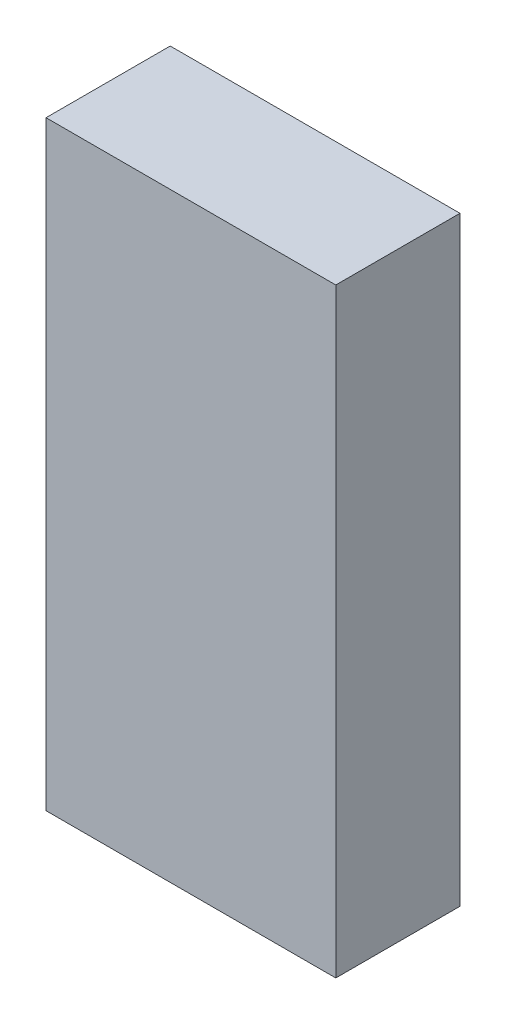
SolidWorks part; units mm, degrees
ref_plane "Front Plane" through (0, 0, 0) normal (0, 0, 1) x (1, 0, 0)
ref_plane "Top Plane" through (0, 0, 0) normal (0, 1, 0) x (1, 0, 0)
ref_plane "Right Plane" through (0, 0, 0) normal (1, 0, 0) x (0, 0, -1)
sketch "Sketch1" plane through (0, 0, 0) normal (0, 0, 1) x (1, 0, 0)
  line L1 (0, 0) -> (14, 0)
  line L2 (0, 0) -> (0, 29)
  line L3 (0, 29) -> (14, 29)
  line L4 (14, 0) -> (14, 29)
  dimension "D1" = 29
  dimension "D2" = 14
extrude "Boss-Extrude1" add sketch "Sketch1" along normal blind 6
